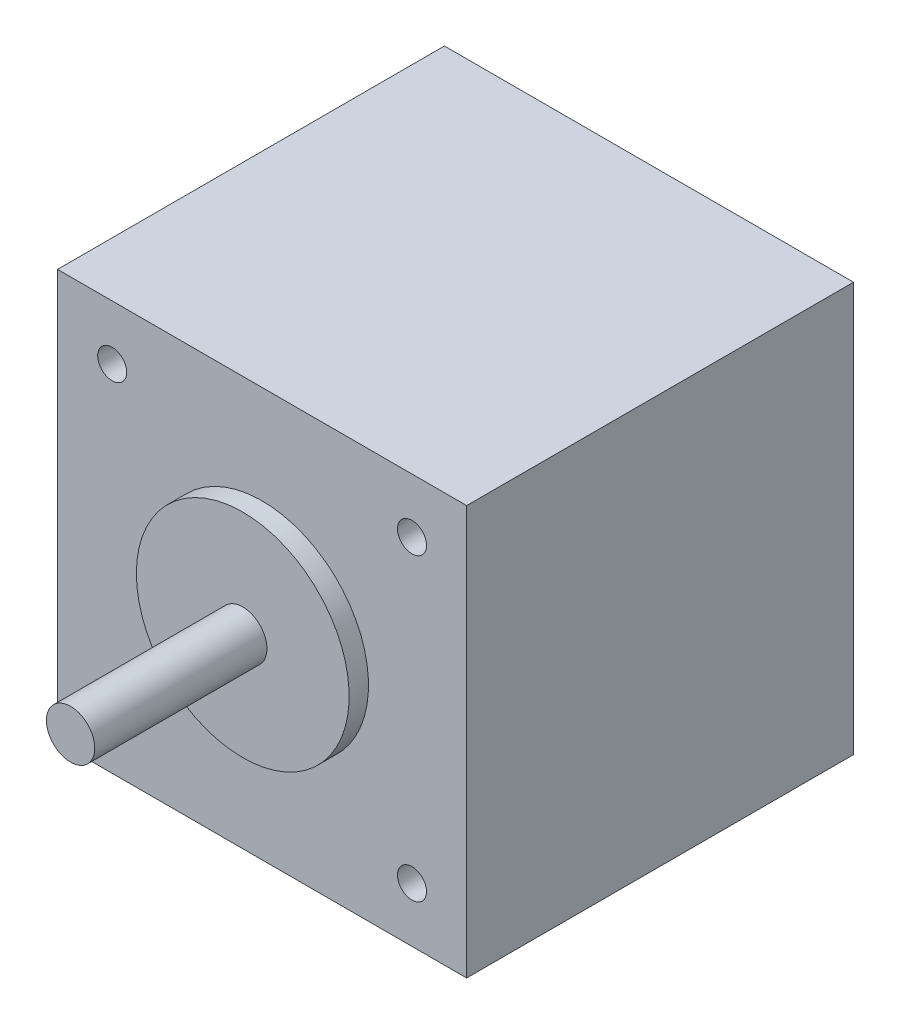
SolidWorks part; units mm, degrees
ref_plane "Спереди" through (0, 0, 0) normal (0, 0, 1) x (1, 0, 0)
ref_plane "Сверху" through (0, 0, 0) normal (0, 1, 0) x (1, 0, 0)
ref_plane "Справа" through (0, 0, 0) normal (1, 0, 0) x (0, 0, -1)
other "Configuration Table"
sketch "Эскиз1" plane through (0, 0, 0) normal (0, 0, 1) x (1, 0, 0)
  line L1 (-21.15, -21.15) -> (21.15, -21.15)
  line L2 (-21.15, -21.15) -> (-21.15, 21.15)
  line L3 (-21.15, 21.15) -> (21.15, 21.15)
  line L4 (21.15, -21.15) -> (21.15, 21.15)
  line L5 (-21.15, -21.15) -> (21.15, 21.15) construction
  line L6 (-21.15, 21.15) -> (21.15, -21.15) construction
  point P0 (0, 0)
  dimension "D1" = 42.3
  dimension "D2" = 42.3
extrude "Корпус" add sketch "Эскиз1" along normal blind 40
sketch "Эскиз2" plane through (0, 0, 0) normal (0, 0, 1) x (1, 0, 0)
  circle A0 centre (0, 0) radius 2.5
extrude "Вал_ПРЕДВ" add sketch "Эскиз2" along normal blind 59.8
sketch "Эскиз3" plane through (0, 0, 0) normal (0, 0, 1) x (1, 0, 0)
  circle A0 centre (0, 0) radius 11
  dimension "D1" = 22
extrude "Буртик_ПРЕДВ" add sketch "Эскиз3" along normal blind 42
sketch "Эскиз4" plane through (0, 0, 0) normal (0, 0, 1) x (1, 0, 0)
  circle A0 centre (0, 0) radius 8
  dimension "D1" = 16
sketch "Эскиз5" plane through (0, 0, 0) normal (0, 0, 1) x (1, 0, 0)
  circle A0 centre (-15.5, -15.5) radius 1.5
  circle A1 centre (-15.5, 15.5) radius 1.5
  circle A2 centre (15.5, -15.5) radius 1.5
  circle A3 centre (15.5, 15.5) radius 1.5
  dimension "D1" = 3
  dimension "D2" = 3
  dimension "D3" = 3
  dimension "D4" = 3
extrude "Крепеж_М3_ПРЕДВ" cut sketch "Эскиз5" against normal blind 4.5 from offset 40
equation "\"Мотор X ширина корпуса\"= 42.3"
equation "\"Мотор X высота корпуса\"= 42.3"
equation "\"Мотор X длина корпуса\"= 40"
equation "\"Мотор X вылет вала\"= 19.8"
equation "\"Мотор Y ширина корпуса\"= 42.3"
equation "\"Мотор Y высота корпуса\"= 42.3"
equation "\"Мотор Y длина корпуса\"= 48"
equation "\"Мотор Y вылет вала\"= 30"
equation "\"Мотор Z ширина корпуса\"= 42"
equation "\"Мотор Z высота корпуса\"= 42"
equation "\"Мотор Z длина корпуса\"= 40"
equation "\"Мотор Z вылет вала\"= 23"
equation "\"Мотор диаметр вала ПРЕДВ\"= 5"
equation "\"Мотор шаг крепления ПРЕДВ\"= 31"
equation "\"Мотор диаметр отверстий ПРЕДВ\"= 3"
equation "\"Мотор глубина отверстий ПРЕДВ\"= 4.5"
equation "\"Мотор диаметр буртика ПРЕДВ\"= 22"
equation "\"Мотор высота буртика ПРЕДВ\"= 2"
equation "\"Мотор диаметр шкива ПРЕДВ\"= 16"
equation "\"Мотор длина шкива ПРЕДВ\"= 12"
equation "\"Мотор отступ шкива ПРЕДВ\"= 5"
equation "\"Мотор X шаг градусов\"= 1.8"
equation "\"Мотор Y шаг градусов\"= 1.8"
equation "\"Мотор Z шаг градусов\"= 1.8"
equation "\"Мотор Y диаметр ротора\"= 25.78"
equation "\"D1@Эскиз1\" = \"Мотор X ширина корпуса\""
equation "\"D1@Корпус\" = \"Мотор X длина корпуса\""
equation "\"D1@Эскиз2\" = \"Мотор диаметр вала ПРЕДВ\""
equation "\"D1@Вал_ПРЕДВ\" = \"Мотор X длина корпуса\" + \"Мотор X вылет вала\""
equation "\"D1@Эскиз3\" = \"Мотор диаметр буртика ПРЕДВ\""
equation "\"D1@Буртик_ПРЕДВ\" = \"Мотор X длина корпуса\" + \"Мотор высота буртика ПРЕДВ\""
equation "\"D1@Эскиз4\" = \"Мотор диаметр шкива ПРЕДВ\""
equation "\"D1@Эскиз5\" = \"Мотор диаметр отверстий ПРЕДВ\""
equation "\"D2@Эскиз5\" = \"Мотор диаметр отверстий ПРЕДВ\""
equation "\"D3@Эскиз5\" = \"Мотор диаметр отверстий ПРЕДВ\""
equation "\"D4@Эскиз5\" = \"Мотор диаметр отверстий ПРЕДВ\""
equation "\"D1@Крепеж_М3_ПРЕДВ\" = \"Мотор глубина отверстий ПРЕДВ\""
equation "\"D19@Крепеж_М3_ПРЕДВ\" = \"Мотор X длина корпуса\""
equation "\"Ширина груза\"= 160"
equation "\"Глубина груза\"= 240"
equation "\"Высота груза\"= 160"
equation "\"Ширина ячейки\"= \"Ширина груза\" + 10"
equation "\"Глубина ячейки\"= \"Глубина груза\" + 10"
equation "\"Высота ячейки\"= \"Высота груза\" + 10 + 13"
equation "\"Колво ячеек ширина\"= 2"
equation "\"Колво ячеек высота\"= 2"
equation "\"Толщина стенки\" = \"Толщина тонких панелей\""
equation "\"Крепление дверцы\"= 5 "
equation "\"Ширина рейки\"= \"Толщина шестерни\""
equation "\"Высота рейки\"= 20"
equation "\"Высота пола\" = 2*\"Толщина тонких панелей\""
equation "\"Колво полозьев\"= 5"
equation "\"Отступ рейки\"= 20"
equation "\"Глубина каретки\"= \"Глубина ячейки\" + 30 + \"Мотор Y высота корпуса\" + 20"
equation "\"Отступ шпильки\"= 26"
equation "\"Диаметр шпильки\"= 5"
equation "\"Длинна шпильки\" = (\"Высота ячейки\"+\"Толщина горизонтальных плит\"+\"Высота пола\")*\"Колво ячеек высота\"+2*(\"Толщина горизонтальных плит\"+\"Отступ рейки\")"
equation "\"Ширина пластины\"= 50  "
equation "\"Высота зона выгрузки\"= \"Высота ячейки\" * 2 + \"Толщина стенки\" * 2"
equation "\"Колво выгрузки\"= 1"
equation "\"Отступ крепления мотора фиксации\" = (\"Ширина пластины\"+20-\"Толщина вертикальных стенок\")/2"
equation "\"Диаметр оси\"= 10"
equation "\"Диаметр ролика\"= 20"
equation "\"Колво роликов\"= 10"
equation "\"Шаг роликов\"= \"Диаметр ролика\" + 20"
equation "\"Ширина ячейки выгрузки\" = \"Ширина ячейки\"+\"Толщина вертикальных стенок\"+2*\"Отступ крепления мотора фиксации\""
equation "\"Длинна рейки\" = (\"Ширина ячейки\"+\"Толщина вертикальных стенок\"+\"Крепление дверцы\")*\"Колво ячеек ширина\"+\"Ширина ячейки выгрузки\"*\"Колво выгрузки\"+\"Толщина вертикальных стенок\"+2*\"Отступ крепления мотора фиксации\"-\"Крепление дверцы\"*\"Колво ячеек ширина\""
equation "\"Толщина шестерни\"= 10"
equation "\"Толщина тонких панелей\" = 6"
equation "\"Толщина вертикальных стенок\" = 6"
equation "\"Толщина горизонтальных плит\" = 6"
equation "\"Базовая высота корпуса\"= (\"Высота ячейки\"+\"Толщина тонких панелей\"+\"Высота пола\")*\"Колво ячеек высота\"+6*\"Толщина тонких панелей\"+\"Мотор X ширина корпуса\"+\"Мотор Y ширина корпуса\"+75"
equation "\"Высота корпуса\"= (\"Высота ячейки\"+\"Толщина горизонтальных плит\"+\"Высота пола\")*\"Колво ячеек высота\"+2*\"Толщина горизонтальных плит\"+4*\"Толщина тонких панелей\"+\"Мотор X ширина корпуса\"+\"Мотор Y ширина корпуса\"+75"
equation "\"Смещение центра корпуса\"= (\"Высота корпуса\"-\"Базовая высота корпуса\")/2-(\"Толщина горизонтальных плит\"-\"Толщина тонких панелей\")"
equation "\"Отметка пола\"= -\"Базовая высота корпуса\"/2+\"Толщина тонких панелей\""
equation "\"Отметка потолка\"= \"Отметка пола\"+\"Высота корпуса\"-2*\"Толщина горизонтальных плит\""
equation "\"Отметка верхней полки\"= \"Отметка потолка\"-(28+\"Толщина тонких панелей\")-\"Высота ячейки\"-\"Высота пола\""
equation "\"Отметка нижней полки\"= \"Отметка верхней полки\"-\"Высота ячейки\"-\"Высота пола\"-\"Толщина горизонтальных плит\""
